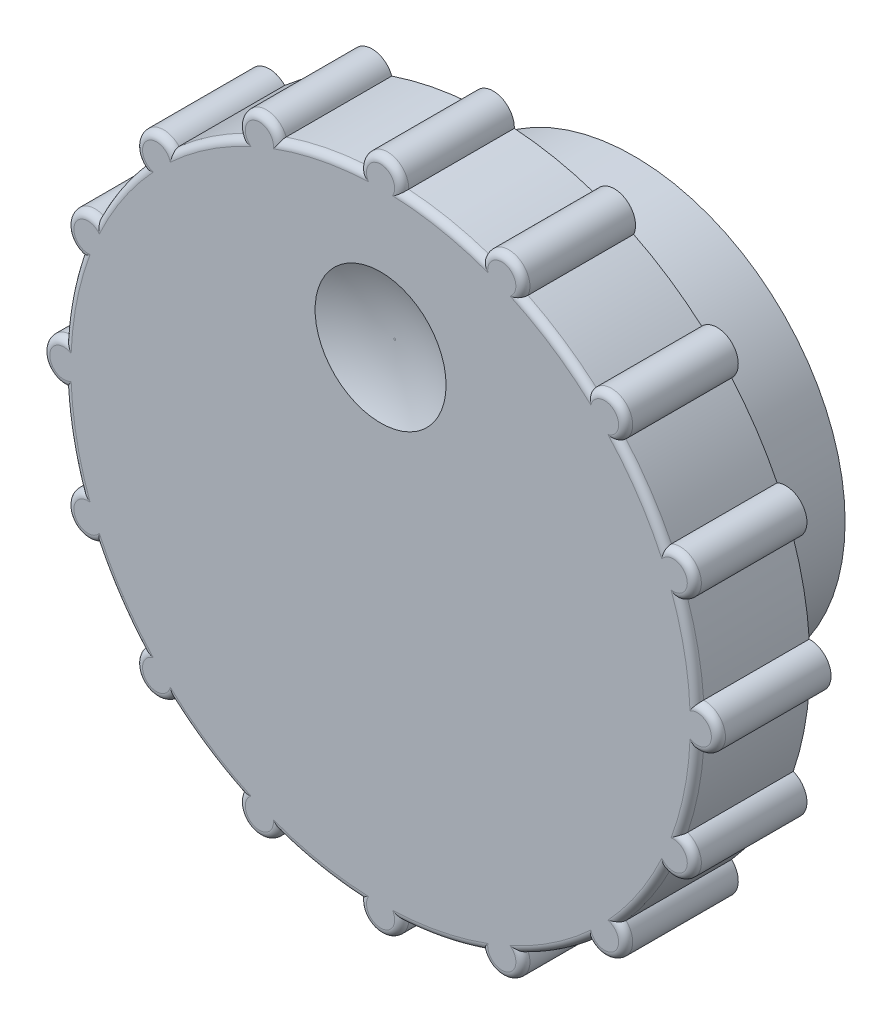
SolidWorks part; units mm, degrees
ref_plane "Спереди" through (0, 0, 0) normal (0, 0, 1) x (1, 0, 0)
ref_plane "Сверху" through (0, 0, 0) normal (0, 1, 0) x (1, 0, 0)
ref_plane "Справа" through (0, 0, 0) normal (1, 0, 0) x (0, 0, -1)
sketch "Эскиз1" plane through (0, 0, 0) normal (0, 0, 1) x (1, 0, 0)
  line L0 (2.8849, 1.4967) -> (-2.8849, 1.4967)
  circle A0 centre (0, 0) radius 15
  arc A1 (-2.8849, 1.4967) -> (2.8849, 1.4967) centre (0, 0) ccw
  dimension "D1" = 30
  dimension "D2" = 6.5
extrude "Бобышка-Вытянуть1" add sketch "Эскиз1" along normal blind 10
sketch "Эскиз2" plane through (0, 0, 10) normal (0, 0, 1) x (1, 0, 0)
  arc A0 (-1.4992, 22.45) -> (-7.2062, 21.3148) centre (0, 0) ccw
  arc A1 (1.4992, 22.45) -> (-1.4992, 22.45) centre (0, 22.5) ccw
  arc A2 (9.9763, 20.1674) -> (7.2062, 21.3148) centre (8.6104, 20.7873) ccw
  arc A3 (16.9346, 14.8145) -> (14.8145, 16.9346) centre (15.9099, 15.9099) ccw
  arc A4 (21.3148, 7.2062) -> (20.1674, 9.9763) centre (20.7873, 8.6104) ccw
  arc A5 (22.45, -1.4992) -> (22.45, 1.4992) centre (22.5, 0) ccw
  arc A6 (20.1674, -9.9763) -> (21.3148, -7.2062) centre (20.7873, -8.6104) ccw
  arc A7 (14.8145, -16.9346) -> (16.9346, -14.8145) centre (15.9099, -15.9099) ccw
  arc A8 (7.2062, -21.3148) -> (9.9763, -20.1674) centre (8.6104, -20.7873) ccw
  arc A9 (-1.4992, -22.45) -> (1.4992, -22.45) centre (0, -22.5) ccw
  arc A10 (-9.9763, -20.1674) -> (-7.2062, -21.3148) centre (-8.6104, -20.7873) ccw
  arc A11 (-16.9346, -14.8145) -> (-14.8145, -16.9346) centre (-15.9099, -15.9099) ccw
  arc A12 (-21.3148, -7.2062) -> (-20.1674, -9.9763) centre (-20.7873, -8.6104) ccw
  arc A13 (-22.45, 1.4992) -> (-22.45, -1.4992) centre (-22.5, 0) ccw
  arc A14 (-20.1674, 9.9763) -> (-21.3148, 7.2062) centre (-20.7873, 8.6104) ccw
  arc A15 (-14.8145, 16.9346) -> (-16.9346, 14.8145) centre (-15.9099, 15.9099) ccw
  arc A16 (-7.2062, 21.3148) -> (-9.9763, 20.1674) centre (-8.6104, 20.7873) ccw
  arc A17 (7.2062, 21.3148) -> (1.4992, 22.45) centre (0, 0) ccw
  arc A18 (14.8145, 16.9346) -> (9.9763, 20.1674) centre (0, 0) ccw
  arc A19 (20.1674, 9.9763) -> (16.9346, 14.8145) centre (0, 0) ccw
  arc A20 (22.45, 1.4992) -> (21.3148, 7.2062) centre (0, 0) ccw
  arc A21 (-9.9763, 20.1674) -> (-14.8145, 16.9346) centre (0, 0) ccw
  arc A22 (-16.9346, 14.8145) -> (-20.1674, 9.9763) centre (0, 0) ccw
  arc A23 (-21.3148, 7.2062) -> (-22.45, 1.4992) centre (0, 0) ccw
  arc A24 (-22.45, -1.4992) -> (-21.3148, -7.2062) centre (0, 0) ccw
  arc A25 (-20.1674, -9.9763) -> (-16.9346, -14.8145) centre (0, 0) ccw
  arc A26 (-14.8145, -16.9346) -> (-9.9763, -20.1674) centre (0, 0) ccw
  arc A27 (-7.2062, -21.3148) -> (-1.4992, -22.45) centre (0, 0) ccw
  arc A28 (1.4992, -22.45) -> (7.2062, -21.3148) centre (0, 0) ccw
  arc A29 (9.9763, -20.1674) -> (14.8145, -16.9346) centre (0, 0) ccw
  arc A30 (16.9346, -14.8145) -> (20.1674, -9.9763) centre (0, 0) ccw
  arc A31 (21.3148, -7.2062) -> (22.45, -1.4992) centre (0, 0) ccw
  point P54 (0, 0)
  dimension "D1" = 45
  dimension "D2" = 3
  dimension "D3" = 16
extrude "Бобышка-Вытянуть2" add sketch "Эскиз2" along normal blind 8 contours A21 A15 A22 A14 A23 A13 A24 A12 A25 A11 A26 A10 A27 A9 A28 A8 A29 A7 A30 A6 A31 A5 A20 A4 A19 A3 A18 A2 A17 A1 A0 A16
sketch "Эскиз3" plane through (0, 0, 18) normal (0, 0, 1) x (1, 0, 0)
  circle A0 centre (0, 12.2235) radius 4.6518
fillet "Скругление2" radius 0.5 32 edges at (-4.3895, 22.0677, 18) (0, 24, 18) (4.3895, 22.0677, 18) (9.1844, 22.1731, 18) (12.5003, 18.7081, 18) (16.9706, 16.9706, 18) (18.7081, 12.5003, 18) (22.1731, 9.1844, 18) (22.0677, 4.3895, 18) (24, 0, 18) (22.0677, -4.3895, 18) (22.1731, -9.1844, 18) (18.7081, -12.5003, 18) (16.9706, -16.9706, 18) (12.5003, -18.7081, 18) (9.1844, -22.1731, 18) (4.3895, -22.0677, 18) (0, -24, 18) (-4.3895, -22.0677, 18) (-9.1844, -22.1731, 18) (-12.5003, -18.7081, 18) (-16.9706, -16.9706, 18) (-18.7081, -12.5003, 18) (-22.1731, -9.1844, 18) (-22.0677, -4.3895, 18) (-24, 0, 18) (-22.0677, 4.3895, 18) (-22.1731, 9.1844, 18) (-18.7081, 12.5003, 18) (-16.9706, 16.9706, 18) (-12.5003, 18.7081, 18) (-9.1844, 22.1731, 18)
extrude "Вырез-Вытянуть2" cut sketch "Эскиз3" against normal blind 1 contours A0
fillet "Скругление3" radius 11 1 edges at (4.6518, 12.2235, 17)
